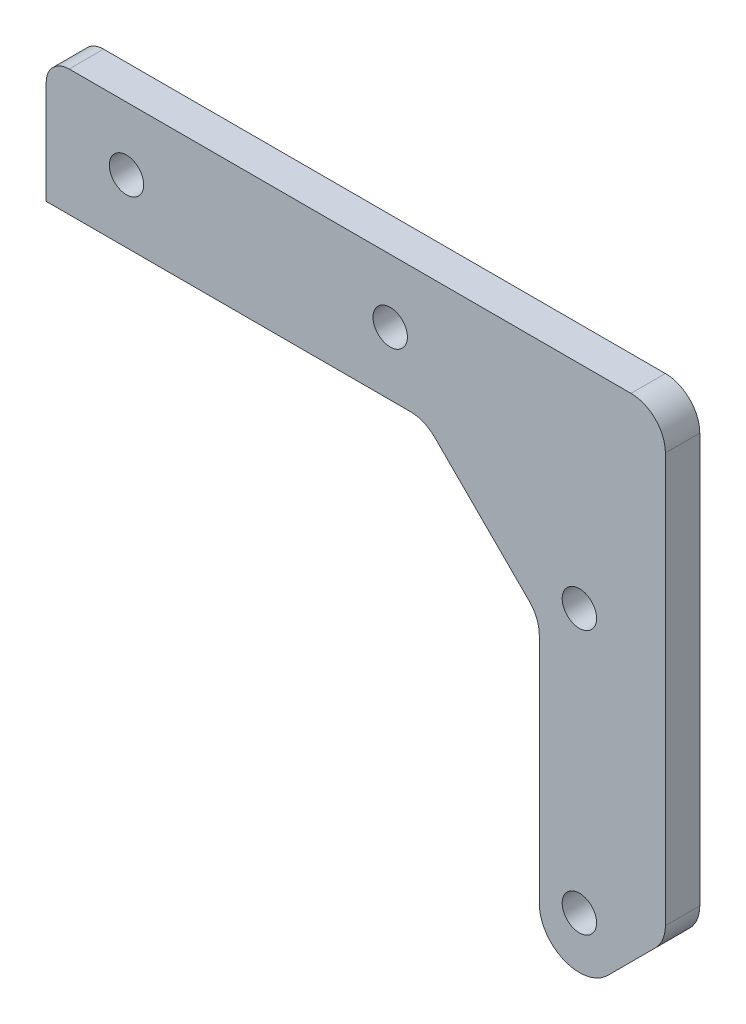
SolidWorks part; units mm, degrees
ref_plane "Спереди" through (0, 0, 0) normal (0, 0, 1) x (1, 0, 0)
ref_plane "Сверху" through (0, 0, 0) normal (0, 1, 0) x (1, 0, 0)
ref_plane "Справа" through (0, 0, 0) normal (1, 0, 0) x (0, 0, -1)
sketch "Эскиз1" plane through (0, 0, 0) normal (0, 0, 1) x (1, 0, 0)
  line L0 (-48.5, 0) -> (5.5, 0) construction
  line L1 (-2, 5.5) -> (-2, -46.5) construction
  line L2 (-48.5, 5.5) -> (-48.5, -5.5)
  line L3 (-48.5, -5.5) -> (-15.5, -5.5)
  line L4 (-5.5, -46.5) -> (5.5, -46.5) construction
  line L5 (-5.5, -15.5) -> (-5.5, -37)
  line L6 (5.5, -34.4497) -> (5.5, 5.5)
  line L7 (5.5, 5.5) -> (-48.5, 5.5)
  line L8 (-15.5, -5.5) -> (-5.5, -15.5)
  line L9 (0, 5.5) -> (0, -46.5) construction
  line L10 (0.4749, -39.4749) -> (5.5, -34.4497)
  line L11 (-5.5, -37) -> (-5.5, -46.5) construction
  line L12 (5.5, -34.4497) -> (5.5, -46.5) construction
  arc A0 (-5.5, -37) -> (0.4749, -39.4749) centre (-2, -37) ccw
  circle A4 centre (-18.5, 0) radius 1.5
  circle A5 centre (-41.5, 0) radius 1.5
  circle A6 centre (-2, -13) radius 1.5
  circle A7 centre (-2, -36) radius 1.5
  dimension "D4" = 11
  dimension "D7" = 13
  dimension "D12" = 3
  dimension "D10" = 45
  dimension "D13" = 24
  dimension "D1" = 11
  dimension "D2" = 43
  dimension "D3" = 52
  dimension "D5" = 10
  dimension "D6" = 45
  dimension "D8" = 3.5
  dimension "D9" = 7
  dimension "D11" = 23
  dimension "D16" = 23
extrude "тело" add sketch "Эскиз1" along normal blind 3
fillet "Fillet1" radius 3 4 edges at (5.5, 5.5, 1.5) (5.5, -34.4497, 1.5) (-5.5, -15.5, 1.5) (-15.5, -5.5, 1.5)
chamfer "Фаски под шляпки (левая)" [suppressed] distance 1.5 angle 45
chamfer "Фаски под шляпки (правая)" [suppressed] distance 1.5 angle 45
fillet "Скругление1" radius 2 1 edges at (-48.5, 5.5, 1.5)
